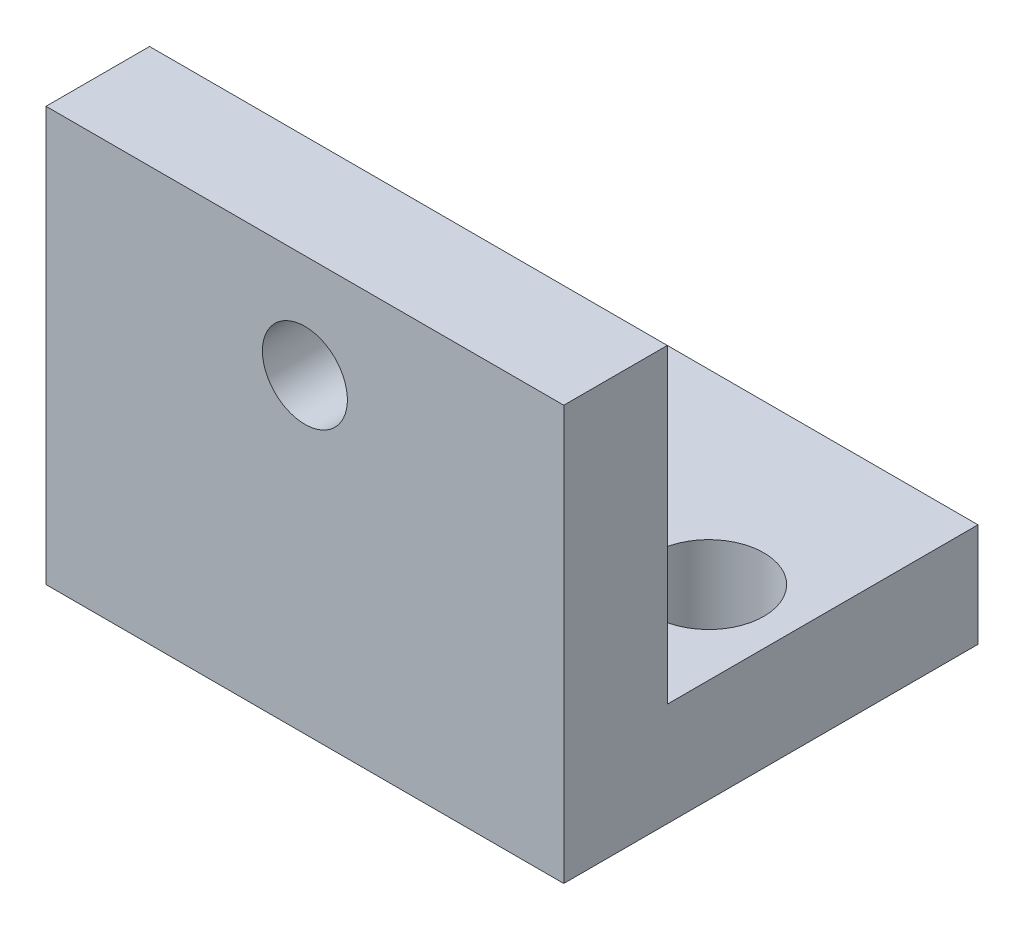
SolidWorks part; units mm, degrees
material "1023 Carbon Steel Sheet (SS)"
ref_plane "Front Plane" through (0, 0, 0) normal (0, 0, 1) x (1, 0, 0)
ref_plane "Top Plane" through (0, 0, 0) normal (0, 1, 0) x (1, 0, 0)
ref_plane "Right Plane" through (0, 0, 0) normal (1, 0, 0) x (0, 0, -1)
sketch "Sketch2" plane through (0, 0, 0) normal (1, 0, 0) x (0, 0, -1)
  line L0 (0, 0) -> (25.4, 0)
  line L1 (25.4, 0) -> (25.4, 6.35)
  line L2 (25.4, 6.35) -> (6.35, 6.35)
  line L3 (6.35, 6.35) -> (6.35, 25.4)
  line L4 (6.35, 25.4) -> (0, 25.4)
  line L5 (0, 25.4) -> (0, 0)
  dimension "D1" = 6.35
  dimension "D2" = 6.35
  dimension "D3" = 25.4
  dimension "D4" = 25.4
extrude "Boss-Extrude1" add sketch "Sketch2" along normal blind 31.75
sketch "Sketch3" plane through (0, 0, -6.35) normal (0, 0, -1) x (-1, 0, 0)
  line L1 (0, 6.35) -> (0, 25.4) construction
  line L2 (-31.75, 0) -> (0, 0) construction
  circle A0 centre (-15.875, 19.05) radius 2.6035
  dimension "D6" = 5.207
  dimension "D5" = 19.05
  dimension "D7" = 15.875
extrude "Cut-Extrude1" cut sketch "Sketch3" against normal through all
sketch "Sketch4" plane through (0, 6.35, 0) normal (0, 1, 0) x (1, 0, 0)
  line L0 (0, 25.4) -> (0, 6.35) construction
  line L1 (31.75, 25.4) -> (31.75, 6.35) construction
  line L2 (31.75, 25.4) -> (0, 25.4) construction
  circle A1 centre (5.08, 17.78) radius 3.3782
  circle A2 centre (26.67, 13.97) radius 3.3782
  dimension "D1" = 5.08
  dimension "D3" = 5.08
  dimension "D4" = 6.7564
  dimension "D2" = 6.7564
  dimension "D5" = 7.62
  dimension "D6" = 11.43
extrude "Cut-Extrude2" cut sketch "Sketch4" against normal through all
